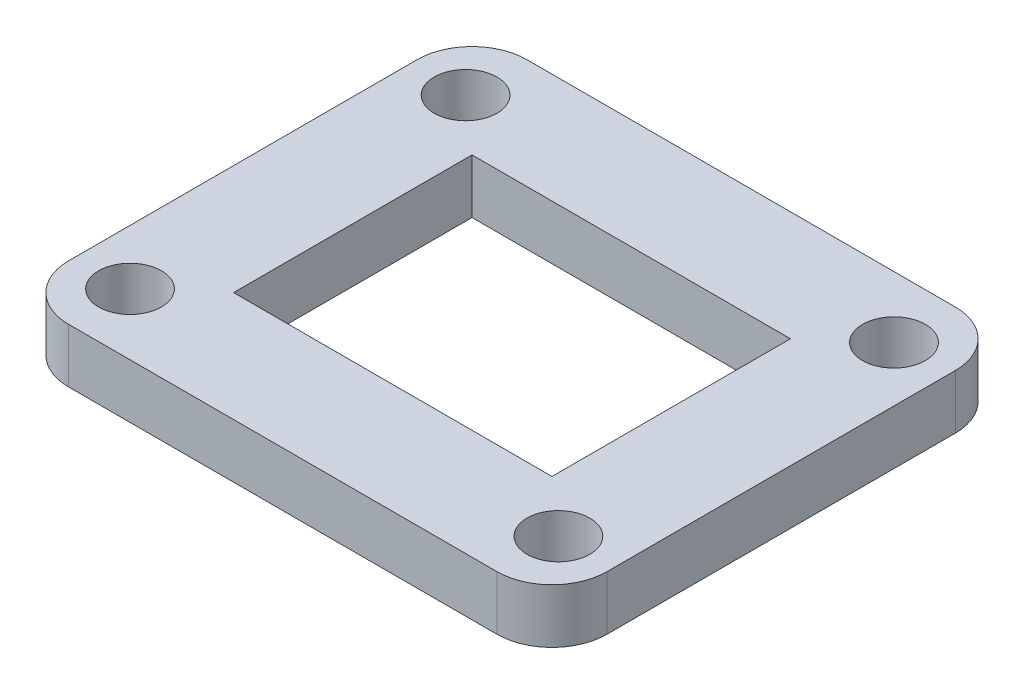
SolidWorks part; units mm, degrees
ref_plane "Front Plane" through (0, 0, 0) normal (0, 0, 1) x (1, 0, 0)
ref_plane "Top Plane" through (0, 0, 0) normal (0, 1, 0) x (1, 0, 0)
ref_plane "Right Plane" through (0, 0, 0) normal (1, 0, 0) x (0, 0, -1)
sketch "Sketch1" plane through (0, 0, 0) normal (0, 1, 0) x (1, 0, 0)
  line L0 (-11.15, 8.35) -> (11.15, 8.35)
  line L1 (-15, -16.05) -> (15, -16.05)
  line L2 (-18.85, -12.2) -> (-18.85, 12.2)
  line L3 (-15, 16.05) -> (15, 16.05)
  line L4 (18.85, -12.2) -> (18.85, 12.2)
  line L5 (-18.85, -16.05) -> (18.85, 16.05) construction
  line L6 (-18.85, 16.05) -> (18.85, -16.05) construction
  line L7 (-15, -11.75) -> (15, -11.75) construction
  line L8 (-15, -11.75) -> (-15, 11.75) construction
  line L9 (-15, 11.75) -> (15, 11.75) construction
  line L10 (15, -11.75) -> (15, 11.75) construction
  line L11 (-15, -11.75) -> (15, 11.75) construction
  line L12 (-15, 11.75) -> (15, -11.75) construction
  line L13 (11.15, -8.35) -> (11.15, 8.35)
  line L14 (-11.15, -8.35) -> (11.15, -8.35)
  line L15 (-11.15, -8.35) -> (-11.15, 8.35)
  circle A0 centre (-15, 11.75) radius 2.2
  circle A1 centre (15, 11.75) radius 2.2
  circle A2 centre (15, -11.75) radius 2.2
  circle A3 centre (-15, -11.75) radius 2.2
  arc A4 (15, -16.05) -> (18.85, -12.2) centre (15, -12.2) ccw
  arc A5 (-15, -16.05) -> (-18.85, -12.2) centre (-15, -12.2) cw
  arc A6 (18.85, 12.2) -> (15, 16.05) centre (15, 12.2) ccw
  arc A7 (-18.85, 12.2) -> (-15, 16.05) centre (-15, 12.2) cw
  arc A8 (11.15, 8.35) -> (11.15, 8.35) centre (11.15, 8.35) ccw
  arc A9 (11.15, -8.35) -> (11.15, -8.35) centre (11.15, -8.35) ccw
  arc A10 (-11.15, -8.35) -> (-11.15, -8.35) centre (-11.15, -8.35) cw
  arc A11 (-11.15, 8.35) -> (-11.15, 8.35) centre (-11.15, 8.35) cw
  point P0 (0, 0)
  point P6 (0, 0)
  dimension "D3" = 4.4
  dimension "D6" = 3.85
  dimension "D1" = 30
  dimension "D2" = 23.5
  dimension "D4" = 37.7
  dimension "D5" = 32.1
  dimension "D7" = 7.7
extrude "Boss-Extrude1" add sketch "Sketch1" along normal blind 3.8
